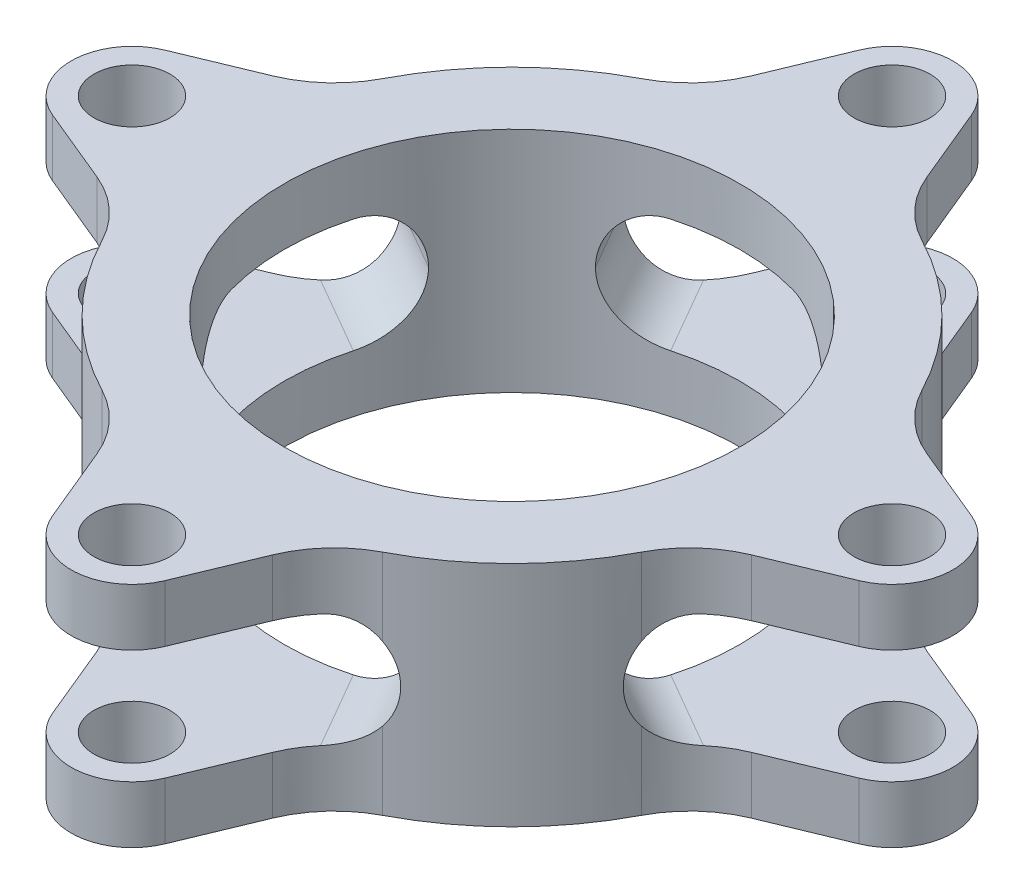
SolidWorks part; units mm, degrees
material "Plain Carbon Steel"
ref_plane "Front Plane" through (0, 0, 0) normal (0, 0, 1) x (1, 0, 0)
ref_plane "Top Plane" through (0, 0, 0) normal (0, 1, 0) x (1, 0, 0)
ref_plane "Right Plane" through (0, 0, 0) normal (1, 0, 0) x (0, 0, -1)
sketch "Sketch1" plane through (0, 0, 0) normal (0, 1, 0) x (1, 0, 0)
  line L0 (0, 132.8019) -> (0, -116.7204) construction
  line L1 (-97.1461, 0) -> (98.7072, 0) construction
  line L2 (-7.391, 53.0615) -> (-13.8219, 37.5361)
  line L3 (7.391, 53.0615) -> (13.8219, 37.5361)
  line L4 (53.0615, 7.391) -> (37.5361, 13.8219)
  line L5 (53.0615, -7.391) -> (37.5361, -13.8219)
  line L6 (7.391, -53.0615) -> (13.8219, -37.5361)
  line L7 (-7.391, -53.0615) -> (-13.8219, -37.5361)
  line L8 (-53.0615, -7.391) -> (-37.5361, -13.8219)
  line L9 (-53.0615, 7.391) -> (-37.5361, 13.8219)
  line L10 (0, 0) -> (13.8219, 37.5361) construction
  circle A0 centre (0, 0) radius 30
  arc A1 (-13.8219, 37.5361) -> (-37.5361, 13.8219) centre (0, 0) ccw
  circle A2 centre (0, 50) radius 5
  circle A4 centre (0, 50) radius 8
  circle A5 centre (50, 0) radius 8
  circle A6 centre (50, 0) radius 5
  circle A7 centre (0, -50) radius 8
  circle A8 centre (0, -50) radius 5
  circle A9 centre (-50, 0) radius 8
  circle A10 centre (-50, 0) radius 5
  arc A11 (37.5361, 13.8219) -> (13.8219, 37.5361) centre (0, 0) ccw
  arc A12 (13.8219, -37.5361) -> (37.5361, -13.8219) centre (0, 0) ccw
  arc A13 (-37.5361, -13.8219) -> (-13.8219, -37.5361) centre (0, 0) ccw
  point P16 (0, 0)
  dimension "D1" = 60
  dimension "D2" = 80
  dimension "D4" = 10
  dimension "D5" = 16
  dimension "D3" = 50
  dimension "D6" = 45
  dimension "D7" = 4
extrude "Boss-Extrude1" add sketch "Sketch1" along normal mid plane 30 contours L8 A13 L7 A7 L6 A12 L5 A5 L4 A11 L3 A4 L2 A1 L9 A9 A0 | A9 | A4 | A5 | A7 | A10 | A2 | A6 | A8 region at (-1.8535, 0, -40.6818)
fillet "Fillet1" radius 15 8 edges at (13.8219, 0, -37.5361) (37.5361, 0, -13.8219) (37.5361, 0, 13.8219) (13.8219, 0, 37.5361) (-13.8219, 0, 37.5361) (-37.5361, 0, 13.8219) (-37.5361, 0, -13.8219) (-13.8219, 0, -37.5361)
sketch "Sketch2" plane through (0, 0, 0) normal (0, 1, 0) x (1, 0, 0)
  line L0 (0, 107.6907) -> (0, -109.0916) construction
  line L1 (-88.9543, 0) -> (87.5534, 0) construction
  line L2 (0, 0) -> (-92.098, 53.1728)
  line L3 (0, 0) -> (-92.098, -53.1728)
  arc A0 (-92.098, -53.1728) -> (-92.098, 53.1728) centre (0, 0) cw
  dimension "D1" = 60
  dimension "D2" = 30
extrude "Cut-Extrude1" cut sketch "Sketch2" against normal mid plane 15
pattern_circular "CirPattern1" count 4 over 360 about axis through (0, 15, 0) along (0, -1, 0) of "Cut-Extrude1"
fillet "Fillet2" radius 7.5 16 edges at (-17.5, 7.5, -30.3109) (-17.5, -7.5, -30.3109) (17.5, 7.5, -30.3109) (17.5, -7.5, -30.3109) (-30.3109, -7.5, 17.5) (-30.3109, 7.5, 17.5) (-30.3109, 7.5, -17.5) (-30.3109, -7.5, -17.5) (30.3109, 7.5, -17.5) (30.3109, -7.5, -17.5) (30.3109, -7.5, 17.5) (30.3109, 7.5, 17.5) (-17.5, 7.5, 30.3109) (-17.5, -7.5, 30.3109) (17.5, 7.5, 30.3109) (17.5, -7.5, 30.3109)
